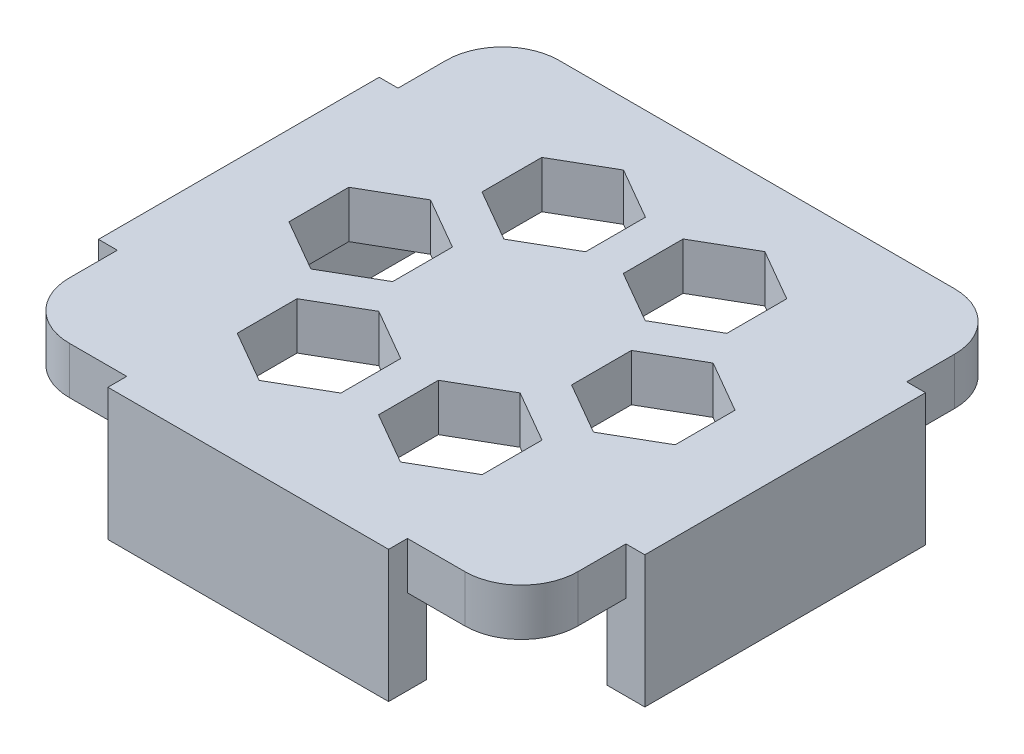
SolidWorks part; units mm, degrees
ref_plane "Front" through (0, 0, 0) normal (0, 0, 1) x (1, 0, 0)
ref_plane "Top" through (0, 0, 0) normal (0, 1, 0) x (1, 0, 0)
ref_plane "Right" through (0, 0, 0) normal (1, 0, 0) x (0, 0, -1)
sketch "Sketch1" plane through (0, 0, 0) normal (0, 1, 0) x (1, 0, 0)
  line L1 (-10.5, -13) -> (10.5, -13)
  line L2 (-13.5, -10) -> (-13.5, 10)
  line L3 (-10.5, 13) -> (10.5, 13)
  line L4 (13.5, -10) -> (13.5, 10)
  line L5 (-13.5, -13) -> (13.5, 13) construction
  line L6 (-13.5, 13) -> (13.5, -13) construction
  arc A0 (10.5, 13) -> (13.5, 10) centre (10.5, 10) cw
  arc A1 (-13.5, 10) -> (-10.5, 13) centre (-10.5, 10) cw
  arc A2 (-10.5, -13) -> (-13.5, -10) centre (-10.5, -10) cw
  arc A3 (10.5, -13) -> (13.5, -10) centre (10.5, -10) ccw
  point P0 (0, 0)
  dimension "D3" = 3
  dimension "D1" = 26
  dimension "D2" = 27
extrude "Boss-Extrude1" add sketch "Sketch1" along normal blind 2.5
sketch "Sketch2" plane through (0, 0, 0) normal (0, -1, 0) x (1, 0, 0)
  line L0 (0, 13) -> (0, -13) construction
  line L1 (-10.5, 13) -> (10.5, 13) construction
  line L2 (10.5, -13) -> (-10.5, -13) construction
  line L3 (-13.5, 0) -> (13.5, 0) construction
  line L4 (-13.5, -10) -> (-13.5, 10) construction
  line L5 (13.5, 10) -> (13.5, -10) construction
  line L6 (-12.5, 7.45) -> (-14.5, 7.45)
  line L7 (12.5, -7.45) -> (14.5, -7.45)
  line L8 (12.5, -7.45) -> (12.5, 7.45)
  line L9 (12.5, 7.45) -> (14.5, 7.45)
  line L10 (14.5, -7.45) -> (14.5, 7.45)
  line L11 (12.5, -7.45) -> (14.5, 7.45) construction
  line L12 (12.5, 7.45) -> (14.5, -7.45) construction
  line L13 (-14.5, -7.45) -> (-14.5, 7.45)
  line L14 (-12.5, -7.45) -> (-14.5, -7.45)
  line L15 (-12.5, -7.45) -> (-12.5, 7.45)
  line L16 (13.5, 0) -> (12.5, 0) construction
  line L17 (7.45, -14) -> (-7.45, -14) construction
  line L18 (7.45, -14) -> (7.45, -12) construction
  line L19 (7.45, -12) -> (-7.45, -12) construction
  line L20 (-7.45, -14) -> (-7.45, -12) construction
  line L21 (7.45, -14) -> (-7.45, -12) construction
  line L22 (7.45, -12) -> (-7.45, -14) construction
  line L23 (0, -12) -> (0, -13) construction
  line L24 (7.45, 12) -> (-7.45, 12)
  line L25 (-7.45, 14) -> (-7.45, 12)
  line L26 (7.45, 14) -> (-7.45, 14)
  line L27 (7.45, 14) -> (7.45, 12)
  point P12 (13.5, 0)
  point P22 (0, -13)
  dimension "D1" = 14.9
  dimension "D2" = 2
  dimension "D3" = 1
extrude "Boss-Extrude2" add sketch "Sketch2" against normal up to vertex (2.5 mm away) and the other way blind 4.5 up to point (-10.5, 2.5, -13)
sketch "Sketch3" plane through (0, 2.5, 0) normal (0, 1, 0) x (1, 0, 0)
  line L0 (0, 13) -> (0, 10) construction
  line L1 (10.5, 13) -> (-10.5, 13) construction
  line L2 (-13.5, 8.725) -> (-10.5, 8.725) construction
  line L3 (-13.5, 10) -> (-13.5, 7.45) construction
  line L4 (13.5, 8.725) -> (10.5, 8.725) construction
  line L5 (13.5, 7.45) -> (13.5, 10) construction
  line L6 (-8.975, -13) -> (-8.975, -10) construction
  line L7 (-10.5, -10) -> (10.5, -10) construction
  line L8 (-10.5, -10) -> (-10.5, 10) construction
  line L9 (-10.5, 10) -> (10.5, 10) construction
  line L10 (10.5, -10) -> (10.5, 10) construction
  line L11 (-10.5, -10) -> (10.5, 10) construction
  line L12 (-10.5, 10) -> (10.5, -10) construction
  line L13 (-10.5, -13) -> (-7.45, -13) construction
  line L14 (1, -4.9075) -> (3.75, -3.3198)
  line L39 (-3.75, 3.3198) -> (-1, 4.9075)
  line L40 (-10.5, 0) -> (10.5, 0) construction
  line L71 (-1, 4.9075) -> (-1, 8.0829)
  line L72 (0, -3.1754) -> (2.75, -1.5877) construction
  line L73 (2.75, -1.5877) -> (2.75, 1.5877) construction
  line L74 (2.75, 1.5877) -> (0, 3.1754) construction
  line L75 (0, 3.1754) -> (-2.75, 1.5877) construction
  line L76 (-2.75, 1.5877) -> (-2.75, -1.5877) construction
  line L77 (-2.75, -1.5877) -> (0, -3.1754) construction
  line L78 (-7.5, -3.1754) -> (-4.75, -1.5877)
  line L79 (-4.75, -1.5877) -> (-4.75, 1.5877)
  line L80 (-4.75, 1.5877) -> (-7.5, 3.1754)
  line L81 (-7.5, 3.1754) -> (-10.25, 1.5877)
  line L82 (-10.25, 1.5877) -> (-10.25, -1.5877)
  line L83 (-10.25, -1.5877) -> (-7.5, -3.1754)
  line L90 (7.5, -3.1754) -> (10.25, -1.5877)
  line L91 (10.25, -1.5877) -> (10.25, 1.5877)
  line L92 (10.25, 1.5877) -> (7.5, 3.1754)
  line L93 (7.5, 3.1754) -> (4.75, 1.5877)
  line L94 (4.75, 1.5877) -> (4.75, -1.5877)
  line L95 (4.75, -1.5877) -> (7.5, -3.1754)
  line L96 (-1, 8.0829) -> (-3.75, 9.6706)
  line L97 (-3.75, 9.6706) -> (-6.5, 8.0829)
  line L98 (-6.5, 8.0829) -> (-6.5, 4.9075)
  line L99 (-6.5, 4.9075) -> (-3.75, 3.3198)
  line L100 (3.75, 3.3198) -> (6.5, 4.9075)
  line L101 (6.5, 4.9075) -> (6.5, 8.0829)
  line L102 (6.5, 8.0829) -> (3.75, 9.6706)
  line L103 (3.75, 9.6706) -> (1, 8.0829)
  line L104 (1, 8.0829) -> (1, 4.9075)
  line L105 (1, 4.9075) -> (3.75, 3.3198)
  line L106 (1, -8.0829) -> (1, -4.9075)
  line L107 (3.75, -9.6706) -> (1, -8.0829)
  line L108 (6.5, -8.0829) -> (3.75, -9.6706)
  line L109 (6.5, -4.9075) -> (6.5, -8.0829)
  line L110 (3.75, -3.3198) -> (6.5, -4.9075)
  line L111 (-6.5, -4.9075) -> (-3.75, -3.3198)
  line L112 (-6.5, -8.0829) -> (-6.5, -4.9075)
  line L113 (-3.75, -9.6706) -> (-6.5, -8.0829)
  line L114 (-1, -8.0829) -> (-3.75, -9.6706)
  line L115 (-1, -4.9075) -> (-1, -8.0829)
  line L116 (-3.75, -3.3198) -> (-1, -4.9075)
  circle A0 centre (0, 0) radius 2.75 construction
  circle A1 centre (-7.5, 0) radius 2.75 construction
  circle A2 centre (7.5, 0) radius 2.75 construction
  circle A3 centre (-3.75, 6.4952) radius 2.75 construction
  circle A4 centre (3.75, 6.4952) radius 2.75 construction
  point P12 (0, 0)
  point P64 (-2.375, 4.1136)
  dimension "D5" = 2
  dimension "D4" = 5.5
  dimension "D1" = 3
  dimension "D2" = 2
  dimension "D3" = 2
  dimension "D6" = 2
  dimension "D7" = 2
  dimension "D8" = 2
  dimension "D9" = 2
extrude "Cut-Extrude1" cut sketch "Sketch3" against normal blind 10
